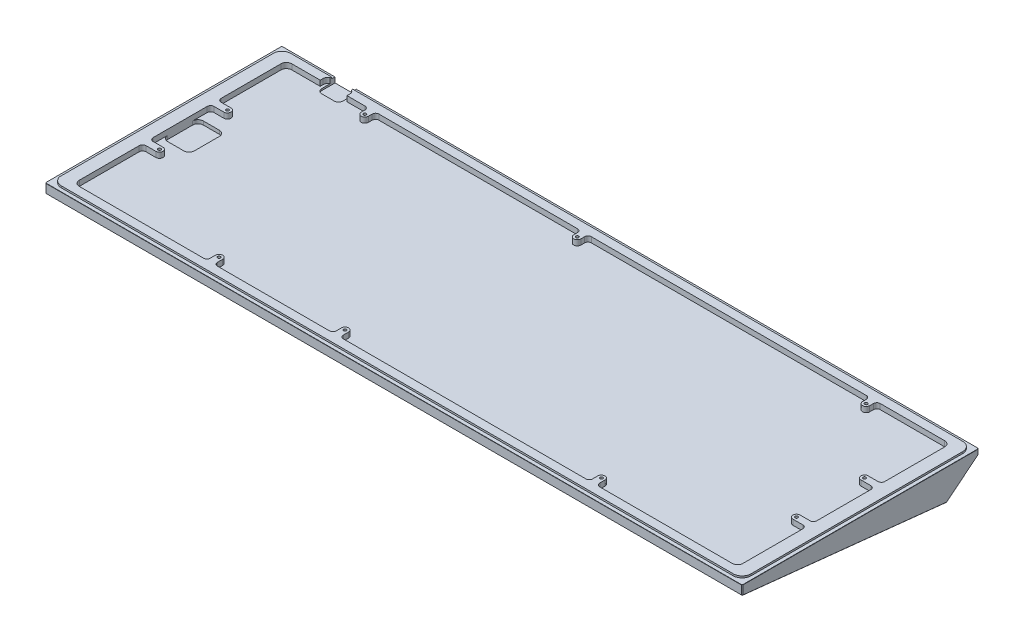
SolidWorks part; units mm, degrees
material "6061-T6 (SS)"
ref_plane "Front Plane" through (0, 0, 0) normal (0, 0, 1) x (1, 0, 0)
ref_plane "Top Plane" through (0, 0, 0) normal (0, 1, 0) x (1, 0, 0)
ref_plane "Right Plane" through (0, 0, 0) normal (1, 0, 0) x (0, 0, -1)
sketch "Sketch1" plane through (0, 0, 0) normal (0, 1, 0) x (1, 0, 0)
  line L1 (0, 0) -> (390.7, 0)
  line L2 (0, 0) -> (0, 132.7)
  line L3 (0, 132.7) -> (390.7, 132.7)
  line L4 (390.7, 0) -> (390.7, 132.7)
  dimension "D1" = 390.7
  dimension "D2" = 132.7
extrude "MainBody" add sketch "Sketch1" along normal blind 18.5
sketch "Sketch2" plane through (0, 18.5, 0) normal (0, 1, 0) x (1, 0, 0)
  line L0 (390.7, 132.7) -> (0, 132.7) construction
  line L1 (2.05, 130.65) -> (388.65, 130.65)
  line L2 (2.05, 130.65) -> (2.05, 2.05)
  line L3 (2.05, 2.05) -> (388.65, 2.05)
  line L4 (388.65, 130.65) -> (388.65, 2.05)
  line L5 (0, 132.7) -> (0, 0) construction
  line L7 (0, 132.7) -> (390.7, 132.7)
  line L8 (0, 132.7) -> (0, 0)
  line L9 (0, 0) -> (390.7, 0)
  line L10 (390.7, 132.7) -> (390.7, 0)
  point P4 (195.35, 130.65)
  point P7 (195.35, 132.7)
  point P8 (2.05, 66.35)
  point P11 (0, 66.35)
  line M5 (0, 132.7) -> (0, 0)
  line M6 (0, 0) -> (390.7, 0)
  line M7 (390.7, 0) -> (390.7, 132.7)
  line M8 (390.7, 132.7) -> (0, 132.7)
  dimension "D1" = 2.05
  dimension "D2" = 2.05
extrude "AligmentLip" cut sketch "Sketch2" against normal blind 1 contours L1 L4 L3 L2 M8 M5 M6 M7
sketch "Sketch3" plane through (0, 0, 0) normal (-1, 0, 0) x (0, 0, 1)
  line L0 (-132.7, 14.5) -> (-114.794, 0)
  line L1 (-132.7, 17.5) -> (-132.7, 0) construction
  line L2 (-132.7, 0) -> (0, 0) construction
  line L3 (-114.794, 0) -> (0, 12.0653)
  line L4 (0, 17.5) -> (0, 0) construction
  line L5 (-132.7, 17.5) -> (0, 17.5) construction
  line L7 (-132.7, 17.5) -> (0, 17.5)
  line L8 (-132.7, 17.5) -> (-132.7, 0)
  line L9 (-132.7, 0) -> (0, 0)
  line L10 (0, 17.5) -> (0, 0)
  line M4 (-132.7, 17.5) -> (-132.7, 0)
  line M5 (-132.7, 0) -> (0, 0)
  line M6 (0, 0) -> (0, 17.5)
  dimension "D1" = 6
  dimension "D2" = 135
  dimension "D3" = 3
extrude "TypingAngle" cut sketch "Sketch3" against normal through all contours L0 M4 M5 | L3 M5 M6
sketch "Sketch4" plane through (0, 18.5, 0) normal (0, 1, 0) x (1, 0, 0)
  line L0 (2.05, 130.65) -> (388.65, 130.65) construction
  line L1 (9.35, 125.9) -> (381.35, 125.9)
  line L2 (9.35, 125.9) -> (9.35, 6.8)
  line L3 (9.35, 6.8) -> (381.35, 6.8)
  line L4 (381.35, 125.9) -> (381.35, 6.8)
  line L5 (2.05, 130.65) -> (2.05, 2.05) construction
  point P4 (195.35, 125.9)
  point P7 (195.35, 130.65)
  point P8 (9.35, 66.35)
  point P11 (2.05, 66.35)
  dimension "D1" = 372
  dimension "D2" = 119.1
extrude "PCBCutout" cut sketch "Sketch4" against normal blind 3
sketch "Sketch13" plane through (0, 15.5, 0) normal (0, 1, 0) x (1, 0, 0)
  line L0 (9.35, 125.9) -> (9.35, 6.8) construction
  line L1 (9.35, 76.35) -> (24.35, 76.35)
  line L2 (9.35, 76.35) -> (9.35, 56.35)
  line L3 (9.35, 56.35) -> (24.35, 56.35)
  line L4 (24.35, 76.35) -> (24.35, 56.35)
  line L5 (2.05, 130.65) -> (2.05, 2.05) construction
  point P6 (9.35, 66.35)
  point P9 (2.05, 66.35)
  dimension "D1" = 15
  dimension "D2" = 20
extrude "Cut-Extrude4" cut sketch "Sketch13" against normal blind 2
fillet "Fillet2" radius 3 8 edges at (381.35, 17, -125.9) (381.35, 17, -6.8) (9.35, 17, -6.8) (9.35, 17, -125.9) (9.35, 14.5, -56.35) (24.35, 14.5, -56.35) (9.35, 14.5, -76.35) (24.35, 14.5, -76.35)
chamfer "Chamfer1" distance 0.5 angle 45 13 edges at (195.35, 12.0653, 0) (390.7, 16, -132.7) (0, 16, -132.7) (0, 7.25, -123.747) (390.7, 7.25, -123.747) (390.7, 6.0327, -57.397) (390.7, 14.7827, 0) (0, 6.0327, -57.397) (0, 14.7827, 0) (0, 17.5, -66.35) (195.35, 17.5, 0) (390.7, 17.5, -66.35) (195.35, 17.5, -132.7)
chamfer "Chamfer2" distance 0.1 angle 45 1 edges at (2.05, 18.5, -66.35)
sketch "Sketch17" plane through (0, 11.9335, -1.2543) normal (0, -0.9945, 0.1045) x (1, 0, 0)
  line L0 (198.25, -60.7388) -> (196.25, -60.7388) construction
  line L1 (198.25, -68.7388) -> (196.25, -68.7388)
  line L2 (198.25, -68.7388) -> (198.25, -52.7388)
  line L3 (198.25, -52.7388) -> (196.25, -52.7388)
  line L4 (196.25, -68.7388) -> (196.25, -52.7388)
  line L5 (202.75, -61.2388) -> (200.75, -61.2388)
  line L6 (202.75, -61.2388) -> (202.75, -48.7388)
  line L7 (202.75, -48.7388) -> (200.75, -48.7388)
  line L8 (200.75, -61.2388) -> (200.75, -48.7388)
  line L9 (193.45, -61.2388) -> (191.45, -61.2388)
  line L10 (193.45, -61.2388) -> (193.45, -53.2388)
  line L11 (193.45, -53.2388) -> (191.45, -53.2388)
  line L12 (191.45, -61.2388) -> (191.45, -53.2388)
  line L13 (189.95, -61.2388) -> (187.95, -61.2388)
  line L14 (189.95, -61.2388) -> (189.95, -53.2388)
  line L15 (189.95, -53.2388) -> (187.95, -53.2388)
  line L16 (187.95, -61.2388) -> (187.95, -53.2388)
  line L17 (186.45, -61.2388) -> (184.45, -61.2388)
  line L18 (186.45, -61.2388) -> (186.45, -53.2388)
  line L19 (186.45, -53.2388) -> (184.45, -53.2388)
  line L20 (184.45, -61.2388) -> (184.45, -53.2388)
  line L25 (202.75, -61.2388) -> (187.95, -61.2388) construction
  line L26 (390.2, -114.1651) -> (0.5, -114.1651) construction
  line L27 (194.25, -64.7388) -> (198.25, -64.7388)
  line L28 (194.25, -62.7388) -> (198.25, -62.7388)
  line L29 (390.7, 1.2612) -> (0, 1.2612) construction
  line L31 (206.25, -53.2388) -> (204.25, -53.2388)
  line L32 (206.25, -53.2388) -> (206.25, -48.7388)
  line L33 (206.25, -48.7388) -> (204.25, -48.7388)
  line L34 (204.25, -53.2388) -> (204.25, -48.7388)
  circle A0 centre (201.75, -63.7388) radius 1
  circle A2 centre (194.25, -63.7388) radius 1
  circle A3 centre (197.25, -67.7388) radius 1
  circle A4 centre (197.25, -53.7388) radius 1
  circle A5 centre (201.75, -60.2388) radius 1
  circle A6 centre (201.75, -49.7388) radius 1
  circle A7 centre (205.25, -52.2388) radius 1
  circle A8 centre (205.25, -49.7388) radius 1
  circle A9 centre (192.45, -60.2388) radius 1
  circle A10 centre (192.45, -54.2388) radius 1
  circle A11 centre (188.95, -60.2388) radius 1
  circle A12 centre (188.95, -54.2388) radius 1
  circle A13 centre (185.45, -60.2388) radius 1
  circle A14 centre (185.45, -54.2388) radius 1
  point P28 (195.35, -61.2388)
  point P29 (201.75, -61.2388)
  point P33 (195.35, -114.1651)
  point P44 (197.25, -68.7388)
  dimension "D12" = 2
  dimension "D13" = 12.5
  dimension "D16" = 2
  dimension "D1" = 16
  dimension "D2" = 2
  dimension "D3" = 0
  dimension "D4" = 2.5
  dimension "D5" = 2.8
  dimension "D6" = 1.5
  dimension "D7" = 1.5
  dimension "D8" = 8
  dimension "D9" = 0.5
  dimension "D10" = 1.5
  dimension "D11" = 2.5
  dimension "D14" = 4.5
  dimension "D15" = 50
  dimension "D17" = 2
  dimension "D18" = 3
  dimension "D19" = 11
extrude "Cut-Extrude5" cut sketch "Sketch17" against normal blind 1 contours A7 | A8 L34 A7 L32 | A8 | A6 | A6 L8 A5 L6 | A5 | A4 | A4 L4 L28 L2 | L28 L4 L27 L2 | A3 L2 L27 L4 | A3 | A2 L27 L4 L28 | A2 | A0 | A9 | A10 L12 A9 L10 | A10 | A12 L16 A11 L14 | A11 | A12 | A14 | A14 L20 A13 L18 | A13
sketch "Sketch18" plane through (0, 0, -132.7) normal (0, 0, -1) x (-1, 0, 0)
  line L1 (-41.8, 18.5) -> (-29.8, 18.5)
  line L2 (-41.8, 18.5) -> (-41.8, 14.5)
  line L3 (-41.8, 14.5) -> (-29.8, 14.5)
  line L4 (-29.8, 18.5) -> (-29.8, 14.5)
  line L5 (0, 17.5) -> (0, 14.7385) construction
  line L6 (-390.2, 14.5) -> (-0.5, 14.5) construction
  line L8 (-2.15, 18.5) -> (-388.65, 18.5) construction
  point P6 (-35.8, 18.5)
  dimension "D1" = 35.8
  dimension "D3" = 12
extrude "Cut-Extrude6" cut sketch "Sketch18" against normal blind 10
sketch "Sketch12" plane through (0, 18.5, 0) normal (0, 1, 0) x (1, 0, 0)
  line L0 (381.35, 125.9) -> (9.35, 125.9) construction
  line L1 (28.3, 125.9) -> (43.3, 125.9)
  line L2 (28.3, 125.9) -> (28.3, 129.85)
  line L3 (28.3, 129.85) -> (43.3, 129.85)
  line L4 (43.3, 125.9) -> (43.3, 129.85)
  line L6 (390.7, 132.7) -> (0, 132.7) construction
  line L7 (41.8, 132.7) -> (29.8, 132.7) construction
  point P6 (35.8, 129.85)
  point P11 (35.8, 132.7)
  dimension "D1" = 15
  dimension "D2" = 2.85
extrude "Cut-Extrude3" cut sketch "Sketch12" against normal up to surface (3 mm away) up to face at (92.04, 15.5, -77.94)
fillet "Fillet1" radius 2.5 4 edges at (43.3, 17, -129.85) (28.3, 17, -129.85) (41.8, 15, -122.7) (29.8, 15, -122.7)
sketch "Sketch19" plane through (0, 15.5, 0) normal (0, 1, 0) x (1, 0, 0)
  line L1 (195.35, 0) -> (195.35, 132.7) construction
  line L6 (378.35, 125.9) -> (43.3, 125.9) construction
  line L7 (55.3, 121.9) -> (59.3, 121.9)
  line L8 (55.3, 121.9) -> (55.3, 125.9)
  line L9 (55.3, 125.9) -> (59.3, 125.9)
  line L10 (59.3, 121.9) -> (59.3, 125.9)
  line L11 (378.35, 125.9) -> (43.3, 125.9) construction
  line L12 (174.4, 121.9) -> (178.4, 121.9)
  line L13 (174.4, 121.9) -> (174.4, 125.9)
  line L14 (174.4, 125.9) -> (178.4, 125.9)
  line L15 (178.4, 121.9) -> (178.4, 125.9)
  line L16 (336.3, 121.9) -> (340.3, 121.9)
  line L17 (336.3, 121.9) -> (336.3, 125.9)
  line L18 (336.3, 125.9) -> (340.3, 125.9)
  line L19 (340.3, 121.9) -> (340.3, 125.9)
  line L20 (381.35, 9.8) -> (381.35, 122.9) construction
  line L21 (373.9, 87.4) -> (381.35, 87.4)
  line L22 (373.9, 87.4) -> (373.9, 83.4)
  line L23 (373.9, 83.4) -> (381.35, 83.4)
  line L24 (381.35, 87.4) -> (381.35, 83.4)
  line L25 (12.35, 6.8) -> (378.35, 6.8) construction
  line L26 (373.9, 49.3) -> (381.35, 49.3)
  line L27 (373.9, 49.3) -> (373.9, 45.3)
  line L28 (373.9, 45.3) -> (381.35, 45.3)
  line L29 (381.35, 49.3) -> (381.35, 45.3)
  line L30 (298.2, 11.6) -> (302.2, 11.6)
  line L31 (298.2, 11.6) -> (298.2, 6.8)
  line L32 (298.2, 6.8) -> (302.2, 6.8)
  line L33 (302.2, 11.6) -> (302.2, 6.8)
  line L34 (12.35, 6.8) -> (378.35, 6.8) construction
  line L35 (158.5, 11.6) -> (154.5, 11.6)
  line L36 (158.5, 11.6) -> (158.5, 6.8)
  line L37 (158.5, 6.8) -> (154.5, 6.8)
  line L38 (154.5, 11.6) -> (154.5, 6.8)
  line L39 (9.35, 59.35) -> (9.35, 9.8) construction
  line L40 (87.9, 11.6) -> (83.9, 11.6)
  line L41 (87.9, 11.6) -> (87.9, 6.8)
  line L42 (87.9, 6.8) -> (83.9, 6.8)
  line L43 (83.9, 11.6) -> (83.9, 6.8)
  line L44 (16.8, 49.3) -> (9.35, 49.3)
  line L45 (16.8, 49.3) -> (16.8, 45.3)
  line L46 (16.8, 45.3) -> (9.35, 45.3)
  line L47 (9.35, 49.3) -> (9.35, 45.3)
  line L48 (9.35, 122.9) -> (9.35, 9.8) construction
  line L49 (16.8, 87.4) -> (9.35, 87.4)
  line L50 (16.8, 87.4) -> (16.8, 83.4)
  line L51 (16.8, 83.4) -> (9.35, 83.4)
  line L52 (9.35, 87.4) -> (9.35, 83.4)
  line L53 (390.2, 132.7) -> (41.8, 132.7) construction
  line L54 (0, 132.2) -> (0, 0.5) construction
  line L55 (0.5, 0) -> (390.2, 0) construction
  circle A0 centre (57.3, 121.9) radius 2
  circle A1 centre (176.4, 121.9) radius 2
  circle A2 centre (338.3, 121.9) radius 2
  circle A3 centre (16.8, 85.4) radius 2
  circle A4 centre (16.8, 47.3) radius 2
  circle A5 centre (85.9, 11.6) radius 2
  circle A6 centre (156.5, 11.6) radius 2
  circle A7 centre (300.2, 11.6) radius 2
  circle A8 centre (373.9, 85.4) radius 2
  circle A9 centre (373.9, 47.3) radius 2
  dimension "D2" = 4
  dimension "D6" = 4
  dimension "D12" = 4
  dimension "D3" = 57.3
  dimension "D4" = 119.1
  dimension "D5" = 161.9
  dimension "D7" = 40.5
  dimension "D8" = 38.1
  dimension "D9" = 36.5
  dimension "D10" = 110.3
  dimension "D11" = 28.6
  dimension "D13" = 70.6
  dimension "D14" = 143.7
  dimension "D15" = 10.8
extrude "Boss-Extrude1" add sketch "Sketch19" along normal up to surface (3 mm away) contours L46 L47 L44 L45 | L51 L52 L49 L50 | A4 | A3 | L10 L9 L8 L7 | A0 | L15 L14 L13 L12 | A1 | L19 L18 L17 L16 | A2 | L21 L24 L23 L22 | A8 | L26 L29 L28 L27 | A9 | L33 L32 L31 L30 | A7 | L36 L37 L38 L35 | A6 | L41 L42 L43 L40 | A5 up to face at (131.54, 18.5, -91.2282)
fillet "Fillet3" radius 1.9 20 edges at (83.9, 17, -6.8) (87.9, 17, -6.8) (158.5, 17, -6.8) (154.5, 17, -6.8) (298.2, 17, -6.8) (302.2, 17, -6.8) (381.35, 17, -45.3) (381.35, 17, -49.3) (381.35, 17, -87.4) (381.35, 17, -83.4) (336.3, 17, -125.9) (340.3, 17, -125.9) (178.4, 17, -125.9) (174.4, 17, -125.9) (59.3, 17, -125.9) (55.3, 17, -125.9) (9.35, 17, -87.4) (9.35, 17, -49.3) (9.35, 17, -45.3) (9.35, 17, -83.4)
sketch "Sketch20" plane through (0, 18.5, 0) normal (0, 1, 0) x (1, 0, 0)
  point P0 (16.8, 47.3)
  point P1 (16.8, 85.4)
  point P3 (85.9, 11.6)
  point P5 (156.5, 11.6)
  point P7 (300.2, 11.6)
  point P9 (373.9, 47.3)
  point P11 (373.9, 85.4)
  point P13 (338.3, 121.9)
  point P15 (176.4, 121.9)
  point P17 (57.3, 121.9)
hole_wizard "M2x0.4 Tapped Hole1" positions "3DSketch3" profile "Sketch22" tap size "M2x0.4" standard "ANSI Metric"
sketch3d "3DSketch3"
  point P0 (57.3, 18.5, -121.9)
  point P3 (176.4, 18.5, -121.9)
  point P6 (16.8, 18.5, -47.3)
  point P9 (16.8, 18.5, -85.4)
  point P12 (85.9, 18.5, -11.6)
  point P15 (156.5, 18.5, -11.6)
  point P18 (300.2, 18.5, -11.6)
  point P21 (373.9, 18.5, -47.3)
  point P24 (373.9, 18.5, -85.4)
  point P27 (338.3, 18.5, -121.9)
sketch "Sketch22" plane through (57.3, 18.5, -121.9) normal (1, 0, 0) x (0, 0, 1)
  line L0 (0, 0) -> (0, 4.4807)
  line L1 (0, 4.4807) -> (0.8, 4)
  line L2 (0.8, 4) -> (0.8, 0)
  line L5 (0.8, 0) -> (0, 0)
  line L10 (0, 4.4807) -> (-0.8, 4) construction
  line L11 (0, -6.35) -> (0, 107.95) construction
  dimension "Tap Drill Dia." = 1.6
  dimension "Tap Drill Depth" = 4
  dimension "Drill Angle" = 118
cosmetic thread "Hole Thread1" parameters "D1"=4, "D2"=2
cosmetic thread "Hole Thread2" parameters "D1"=4, "D2"=2
cosmetic thread "Hole Thread3" parameters "D1"=4, "D2"=2
cosmetic thread "Hole Thread4" parameters "D1"=4, "D2"=2
cosmetic thread "Hole Thread5" parameters "D1"=4, "D2"=2
cosmetic thread "Hole Thread6" parameters "D1"=4, "D2"=2
cosmetic thread "Hole Thread7" parameters "D1"=4, "D2"=2
cosmetic thread "Hole Thread8" parameters "D1"=4, "D2"=2
cosmetic thread "Hole Thread9" parameters "D1"=4, "D2"=2
cosmetic thread "Hole Thread10" parameters "D1"=4, "D2"=2
chamfer "Chamfer3" distance 0.1 angle 45 5 edges at (390.7, 17.5, -66.35) (216, 17.5, -132.7) (15.15, 17.5, -132.7) (195.35, 17.5, 0) (0, 17.5, -66.35)
fillet "Fillet4" radius 5 4 edges at (388.65, 18, -2.05) (388.65, 18, -130.65) (2.05, 17.95, -2.05) (2.05, 17.95, -130.65)
sketch "Sketch23" plane through (0, 11.9335, -1.2543) normal (0, -0.9945, 0.1045) x (1, 0, 0)
  line L0 (390.2, 0.6994) -> (0.5, 0.6994) construction
  line L1 (345.35, -91.7329) -> (45.35, -91.7329)
  line L2 (345.35, -91.7329) -> (345.35, -21.7329)
  line L3 (345.35, -21.7329) -> (45.35, -21.7329)
  line L4 (45.35, -91.7329) -> (45.35, -21.7329)
  line L5 (390.2, -114.1651) -> (390.2, 0.6994) construction
  point P4 (195.35, -21.7329)
  point P7 (195.35, 0.6994)
  point P8 (390.2, -56.7329)
  point P11 (345.35, -56.7329)
  dimension "D1" = 70
  dimension "D2" = 300
extrude "Cut-Extrude7" cut sketch "Sketch23" against normal offset from surface (10.7139 mm away) 2.5
fillet "Fillet5" radius 5 4 edges at (45.35, 7.6724, -93.0446) (45.35, 11.3309, -23.0435) (345.35, 11.3309, -23.0435) (345.35, 7.6724, -93.0446)
